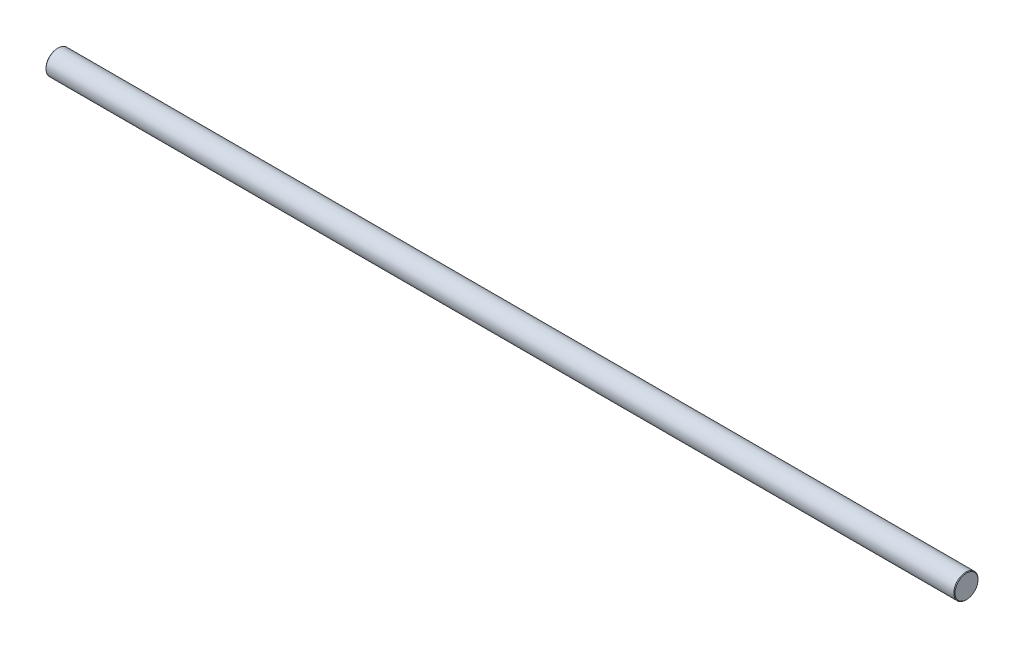
SolidWorks part; units mm, degrees
material "AISI 316 Stainless Steel Sheet (SS)"
ref_plane "Front" through (0, 0, 0) normal (0, 0, 1) x (1, 0, 0)
ref_plane "Top" through (0, 0, 0) normal (0, 1, 0) x (1, 0, 0)
ref_plane "Right" through (0, 0, 0) normal (1, 0, 0) x (0, 0, -1)
sketch "Sketch1" plane through (0, 0, 0) normal (1, 0, 0) x (0, 0, -1)
  line L0 (0, 0) -> (-1.5, 0) construction
  circle A2 centre (0, 0) radius 4
  dimension "Pitch" = 1.5
  dimension "D1" = 8
extrude "Boss-Extrude1" add sketch "Sketch1" along normal blind 300
sketch "Sketch3" plane through (0, 0, 0) normal (-1, 0, 0) x (0, 0, 1)
  circle A1 centre (0, 0) radius 4
  circle A2 centre (0, 0) radius 4
  dimension "D1" = 0
curve "Helix/Spiral1" [suppressed] pitch 1.5 height 301.5 turns 201 parameters "Travel-per-turn"=1.5
sketch "Sketch2" plane through (0, 0, 0) normal (0, 0, 1) x (1, 0, 0)
  line L0 (0, 2.9777) -> (0, 4.375) construction
  line L1 (0, 0) -> (-1.5, 0) construction
  line L2 (0, 2.9777) -> (-0.75, 5.7767) construction
  line L3 (0.75, 5.7767) -> (-0.75, 5.7767) construction
  line L4 (0, 2.9777) -> (0.75, 5.7767) construction
  line L5 (0, 4.375) -> (0, 5.7767) construction
  line L6 (0, 4.375) -> (1.4446, 4.375) construction
  line L7 (-0.3664, 4) -> (0, 4) construction
  line L8 (-1.4585, 4) -> (0, 4)
  line L9 (0, 4.75) -> (-0.3664, 4.75) construction
  line L10 (-0.3664, 4.75) -> (-0.3664, 4) construction
  line L11 (-0.3664, 4.375) -> (0, 4.375) construction
  line L12 (300, 4) -> (0, 4) construction
  line L13 (-0.7293, 4.4185) -> (-0.7293, 4.75) construction
  line L14 (-0.4091, 4.5043) -> (-0.3448, 4.2646)
  line L15 (-1.0495, 4.5043) -> (-1.1137, 4.2646)
  circle A0 centre (-0.7293, 4.4185) radius 0.3315 construction
  circle A1 centre (0, 4.357) radius 0.357 construction
  arc A2 (-0.7293, 4.75) -> (-0.4091, 4.5043) centre (-0.7293, 4.4185) cw
  arc A3 (0, 4) -> (-0.3448, 4.2646) centre (0, 4.357) cw
  arc A4 (-0.7293, 4.75) -> (-1.0495, 4.5043) centre (-0.7293, 4.4185) ccw
  arc A5 (-1.1137, 4.2646) -> (-1.4585, 4) centre (-1.4585, 4.357) cw
  dimension "D3" = 0.714
  dimension "D4" = 0.663
  dimension "Pitch" = 1.5
  dimension "D1" = 30
  dimension "D2" = 0.75
sweep "Sweep1" [suppressed] add profiles "Sketch2" path "Helix/Spiral1"
sketch "Sketch5" plane through (0, 0, 0) normal (-1, 0, 0) x (0, 0, 1)
  circle A5 centre (0, 0) radius 3.8
  dimension "D1" = 7.6
extrude "Cut-Extrude2" cut sketch "Sketch5" against normal through all draft 45 flip side to cut
sketch "Sketch6" plane through (300, 0, 0) normal (1, 0, 0) x (0, 0, -1)
  circle A1 centre (0, 0) radius 3.8
  circle A2 centre (0, 0) radius 3.8
  dimension "D1" = 0
extrude "Cut-Extrude3" cut sketch "Sketch6" against normal through all draft 45 flip side to cut
equation "\"D2@Sketch2\" = \"Pitch@Sketch2\"/2"
equation "\"D3@Sketch2\" = 2*.238*\"Pitch@Sketch2\""
equation "\"D4@Sketch2\" = \"Pitch@Sketch2\"*2*.221"
equation "\"D3@Helix/Spiral1\"=\"Length@Boss-Extrude1\" + \"Travel-per-turn@Helix/Spiral1\""
equation "\"D1@Sketch5\"=\"D1@Sketch1\"*.95"
